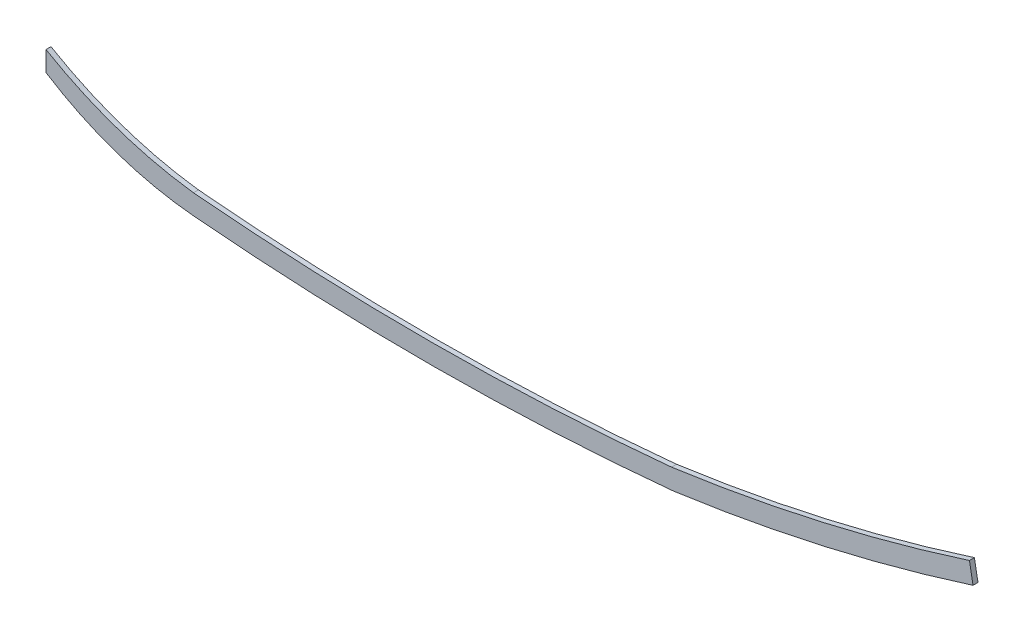
SolidWorks part; units mm, degrees
material "Balsa"
ref_plane "Front Plane" through (0, 0, 0) normal (0, 0, 1) x (1, 0, 0)
ref_plane "Top Plane" through (0, 0, 0) normal (0, 1, 0) x (1, 0, 0)
ref_plane "Right Plane" through (0, 0, 0) normal (1, 0, 0) x (0, 0, -1)
sketch "Sketch2" plane through (0, 0, 0) normal (0, 0, 1) x (1, 0, 0)
  line L0 (0, -93.726) -> (0, -81.026)
  line L2 (93.98, 0) -> (93.98, -379.755) construction
  line L3 (398.3737, -110.9898) -> (402.5381, -142.3403) construction
  line L4 (398.3737, -110.9898) -> (366.1948, 131.2634) construction
  line L7 (590.8643, -81.3536) -> (588.579, -68.7797)
  line L8 (0, 0) -> (672.417, 0) construction
  arc A0 (0, -93.726) -> (93.98, -125.8052) centre (112.6352, 82.55) ccw
  arc A1 (93.98, -125.8052) -> (400.2036, -124.7658) centre (241.5116, 1518.5899) ccw
  arc A2 (400.2036, -124.7658) -> (590.8643, -81.3536) centre (242.7057, 1007.3312) ccw
  arc A3 (95.6211, -113.2301) -> (398.7207, -112.1786) centre (241.5116, 1518.5899) ccw construction
  arc A4 (93.9818, -113.0827) -> (398.7207, -112.1786) centre (241.5116, 1518.5899) ccw
  arc A5 (398.7207, -112.1786) -> (588.579, -68.7797) centre (242.7057, 1007.3312) ccw
  arc A6 (94.4927, -125.8512) -> (400.2036, -124.7658) centre (241.5116, 1518.5899) ccw construction
  arc A7 (398.7207, -112.1786) -> (587.0046, -69.2844) centre (242.7057, 1007.3312) ccw construction
  arc A9 (0, -81.026) -> (93.9818, -113.0827) centre (124.7234, 130.8365) ccw
  spline S0 degree 3 poles (3.7499, -94.8626) (10.597, -99.2271) (17.6385, -103.1401) (32.0968, -110.0953) (39.5136, -113.1375) (50.922, -117.0433) (54.7721, -118.2354) (60.6197, -119.8556) (62.5829, -120.3681) (66.5243, -121.3341) (68.5001, -121.787) (78.4043, -123.9021) (86.408, -125.1172) (94.4926, -125.8525) knots 0 0 0 0 0.25 0.25 0.5 0.5 0.625 0.625 0.6875 0.6875 0.75 0.75 1 1 1 1 construction
  spline S1 degree 3 poles (94.4926, -125.8525) (120.9278, -128.4258) (173.8258, -132.179) (226.7788, -133.168) (266.5142, -132.8729) (279.7628, -132.6016) (299.6408, -131.9345) (306.2677, -131.6688) (319.5231, -131.0505) (326.1536, -130.6977) (359.2877, -128.7173) (385.6949, -126.4433) (412.003, -123.4859) knots 0 0 0 0 0.25 0.5 0.5 0.625 0.625 0.6875 0.6875 0.75 0.75 1 1 1 1 construction
  dimension "D3" = 82.55
  dimension "D4" = 1651
  dimension "D5" = 1143
  dimension "D6" = 79.699
  dimension "D7" = 93.9818
  dimension "D8" = 1638.3286
  dimension "D9" = 245.8488
  dimension "D1" = 12.7
  dimension "D2" = 93.726
extrude "Boss-Extrude1" add sketch "Sketch2" against normal blind 3.175
